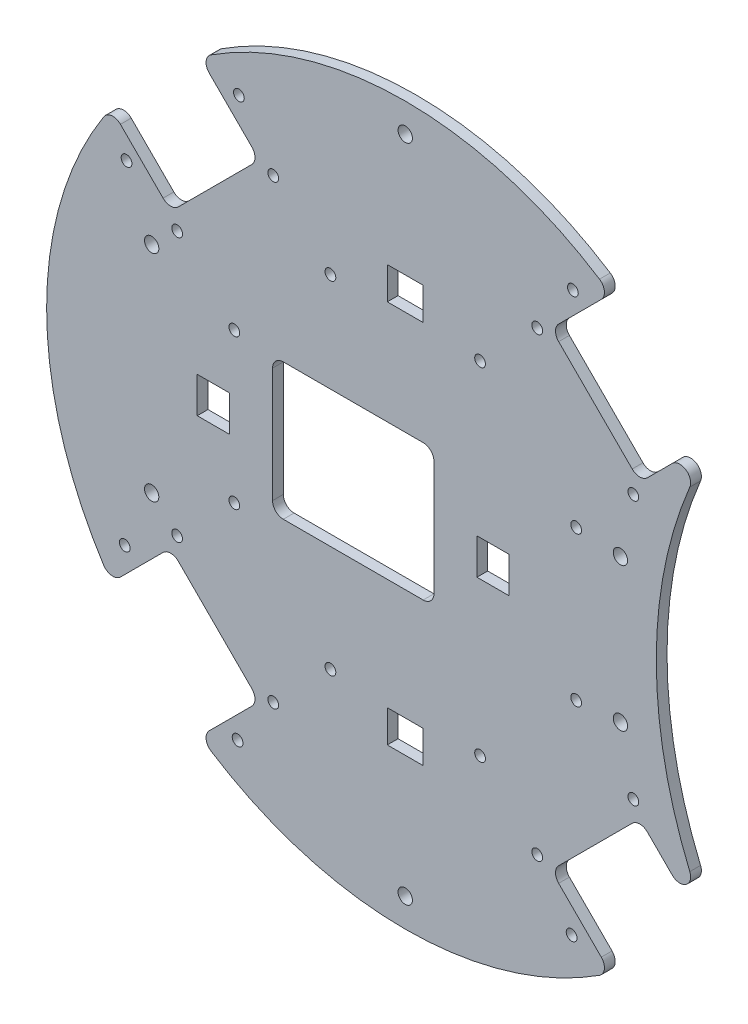
SolidWorks part; units mm, degrees
material "Caoba"
ref_plane "Alzado" through (0, 0, 0) normal (0, 0, 1) x (1, 0, 0)
ref_plane "Planta" through (0, 0, 0) normal (0, 1, 0) x (1, 0, 0)
ref_plane "Vista lateral" through (0, 0, 0) normal (1, 0, 0) x (0, 0, -1)
sketch "Croquis1" plane through (0, 0, 0) normal (0, 0, 1) x (1, 0, 0)
  circle A0 centre (0, 0) radius 100
  dimension "D1" = 200
extrude "Saliente-Extruir1" add sketch "Croquis1" along normal blind 3
sketch "Croquis3" plane through (0, 0, 3) normal (0, 0, 1) x (1, 0, 0)
  line L0 (0, 0) -> (190, 0) construction
  circle A0 centre (190, 0) radius 120
  dimension "D1" = 240
  dimension "D2" = 190
extrude "Cortar-Extruir1" cut sketch "Croquis3" against normal blind 3
sketch "Croquis5" plane through (0, 0, 3) normal (0, 0, 1) x (1, 0, 0)
  line L0 (0, -100) -> (0, 100) construction
  line L1 (-100, 0) -> (70, 0) construction
  line L2 (0, 0) -> (-70.7107, -70.7107) construction
  line L3 (-70.7107, -70.7107) -> (70.7107, 70.7107) construction
  line L4 (0, 0) -> (-70.7107, 70.7107) construction
  line L5 (-70.7107, 70.7107) -> (70.7107, -70.7107) construction
  line L6 (-70.7107, -70.7107) -> (-58.3363, -83.085) construction
  line L9 (-58.3363, -83.085) -> (-83.085, -58.3363)
  line L11 (-83.085, -58.3363) -> (-65.4074, -40.6586)
  line L12 (-65.4074, -40.6586) -> (-40.6586, -65.4074)
  line L13 (-40.6586, -65.4074) -> (-58.3363, -83.085)
  line L14 (-70.7107, 70.7107) -> (-83.085, 58.3363) construction
  line L15 (-83.085, 58.3363) -> (-100, 0) construction
  line L17 (-83.085, 58.3363) -> (-58.3363, 83.085)
  line L18 (-58.3363, 83.085) -> (-40.6586, 65.4074)
  line L19 (-40.6586, 65.4074) -> (-65.4074, 40.6586)
  line L20 (-65.4074, 40.6586) -> (-83.085, 58.3363)
  line L22 (70.7107, -70.7107) -> (58.3363, -83.085) construction
  line L23 (58.3363, -83.085) -> (0, -100) construction
  line L24 (58.3363, -83.085) -> (83.085, -58.3363)
  line L25 (83.085, -58.3363) -> (65.4074, -40.6586)
  line L26 (65.4074, -40.6586) -> (40.6586, -65.4074)
  line L27 (40.6586, -65.4074) -> (58.3363, -83.085)
  line L28 (70.7107, 70.7107) -> (58.3363, 83.085) construction
  line L29 (58.3363, 83.085) -> (0, 100) construction
  line L30 (58.3363, 83.085) -> (83.085, 58.3363)
  line L31 (83.085, 58.3363) -> (65.4074, 40.6586)
  line L32 (65.4074, 40.6586) -> (40.6586, 65.4074)
  line L33 (40.6586, 65.4074) -> (58.3363, 83.085)
  arc A0 (83.4211, 55.1446) -> (83.4211, -55.1446) centre (0, 0) ccw construction
  arc A1 (83.4211, 55.1446) -> (83.4211, -55.1446) centre (190, 0) ccw construction
  point P36 (0, 0)
  dimension "D2" = 17.5
  dimension "D3" = 25
  dimension "D4" = 35
  dimension "D5" = 25
  dimension "D6" = 35
  dimension "D8" = 25
  dimension "D9" = 17.5
  dimension "D7" = 35
  dimension "D10" = 90
  dimension "D11" = 17.5
  dimension "D12" = 17.5
  dimension "D13" = 35
  dimension "D14" = 25
  dimension "D15" = 134.3503
  dimension "D16" = 100
extrude "Cortar-Extruir6" cut sketch "Croquis5" against normal blind 10
sketch "Croquis12" plane through (0, 0, 3) normal (0, 0, 1) x (1, 0, 0)
  line L0 (-53.033, -53.033) -> (-39.9421, -50.0116) construction
  line L1 (-40.6586, -65.4074) -> (-65.4074, -40.6586) construction
  line L2 (-39.9421, -50.0116) -> (-36.8049, -63.6043) construction
  line L3 (-36.8049, -63.6043) -> (-63.6043, -36.8049) construction
  line L4 (-63.6043, -36.8049) -> (-47.6661, -20.8667) construction
  line L6 (53.033, -53.033) -> (-53.033, 53.033) construction
  line L7 (65.4074, -40.6586) -> (40.6586, -65.4074) construction
  line L8 (-65.4074, 40.6586) -> (-40.6586, 65.4074) construction
  line L9 (36.8049, 63.6043) -> (20.8667, 47.6661) construction
  line L10 (63.6043, 36.8049) -> (36.8049, 63.6043) construction
  line L11 (50.0116, 39.9421) -> (63.6043, 36.8049) construction
  line L12 (53.033, 53.033) -> (50.0116, 39.9421) construction
  line L14 (53.033, -53.033) -> (50.2046, -50.2046) construction
  line L15 (50.2046, -50.2046) -> (36.8049, -63.6043) construction
  line L16 (36.8049, -63.6043) -> (63.6043, -36.8049) construction
  line L17 (63.6043, -36.8049) -> (47.6661, -20.8667) construction
  line L19 (-53.033, -53.033) -> (53.033, 53.033) construction
  line L20 (-36.8049, 63.6043) -> (-20.8667, 47.6661) construction
  line L21 (-63.6043, 36.8049) -> (-36.8049, 63.6043) construction
  line L22 (-50.2046, 50.2046) -> (-63.6043, 36.8049) construction
  line L23 (-53.033, 53.033) -> (-50.2046, 50.2046) construction
  circle A0 centre (-63.6043, -36.8049) radius 1.5
  circle A1 centre (-36.8049, -63.6043) radius 1.5
  circle A2 centre (-47.6661, -20.8667) radius 1.5
  circle A3 centre (-20.8667, -47.6661) radius 1.5
  circle A5 centre (47.6661, 20.8667) radius 1.5
  circle A6 centre (20.8667, 47.6661) radius 1.5
  circle A7 centre (63.6043, 36.8049) radius 1.5
  circle A8 centre (36.8049, 63.6043) radius 1.5
  circle A10 centre (20.8667, -47.6661) radius 1.5
  circle A11 centre (47.6661, -20.8667) radius 1.5
  circle A12 centre (63.6043, -36.8049) radius 1.5
  circle A13 centre (36.8049, -63.6043) radius 1.5
  circle A15 centre (-63.6043, 36.8049) radius 1.5
  circle A16 centre (-36.8049, 63.6043) radius 1.5
  circle A17 centre (-20.8667, 47.6661) radius 1.5
  circle A18 centre (-47.6661, 20.8667) radius 1.5
  dimension "D2" = 3
  dimension "D3" = 3
  dimension "D4" = 4
  dimension "D5" = 4
  dimension "D6" = 3
  dimension "D7" = 3
  dimension "D8" = 37.9
  dimension "D9" = 22.54
  dimension "D10" = 22.54
  dimension "D11" = 37.9
  dimension "D12" = 18.95
  dimension "D13" = 18.95
  dimension "D14" = 3
  dimension "D15" = 3
  dimension "D16" = 3
  dimension "D17" = 3
  dimension "D18" = 37.9
  dimension "D19" = 22.54
  dimension "D20" = 22.54
  dimension "D21" = 37.9
  dimension "D22" = 4
  dimension "D1" = 13.95
extrude "Cortar-Extruir7" cut sketch "Croquis12" against normal through all
sketch "Croquis9" plane through (0, 0, 3) normal (0, 0, 1) x (1, 0, 0)
  line L0 (0, 0) -> (-100, 0) construction
  line L5 (0, 100) -> (0, -100) construction
  line L6 (20, 5) -> (29, 5)
  line L7 (20, 5) -> (20, -5)
  line L8 (20, -5) -> (29, -5)
  line L9 (29, 5) -> (29, -5)
  line L10 (-5, -49) -> (5, -49)
  line L11 (-49, 5) -> (-58, 5)
  line L12 (-49, 5) -> (-49, -5)
  line L13 (-49, -5) -> (-58, -5)
  line L14 (-58, 5) -> (-58, -5)
  line L15 (-5, 58) -> (5, 58)
  line L16 (-5, 58) -> (-5, 49)
  line L17 (-5, 49) -> (5, 49)
  line L18 (5, 58) -> (5, 49)
  line L19 (5, -58) -> (5, -49)
  line L20 (-5, -58) -> (5, -58)
  line L21 (-5, -58) -> (-5, -49)
  line L22 (0, 0) -> (70, 0) construction
  line L24 (-52.061, -4) -> (-52.0837, -4) construction
  arc A6 (-81.9939, 57.2451) -> (-81.9939, -57.2451) centre (0, 0) ccw construction
  arc A7 (83.4211, 55.1446) -> (83.4211, -55.1446) centre (190, 0) ccw construction
  dimension "D7" = 49
  dimension "D8" = 49
  dimension "D9" = 20
  dimension "D10" = 49
  dimension "D28" = 5
  dimension "D37" = 5
  dimension "D62" = 9
  dimension "D32" = 10
  dimension "D50" = 5
  dimension "D17" = 9
  dimension "D18" = 10
  dimension "D33" = 5
  dimension "D47" = 10
  dimension "D48" = 9
  dimension "D66" = 9
  dimension "D67" = 10
extrude "Cortar-Extruir5" cut sketch "Croquis9" against normal blind 10
sketch "Croquis13" plane through (0, 0, 3) normal (0, 0, 1) x (1, 0, 0)
  line L0 (0, 100) -> (0, -100) construction
  line L1 (-100, 0) -> (70, 0) construction
  line L2 (-70.7107, 70.7107) -> (70.7107, -70.7107) construction
  line L3 (-70.7093, -70.7093) -> (70.712, 70.712) construction
  line L4 (-70.7107, 70.7107) -> (-70.7093, -70.7093) construction
  line L5 (-70.7093, -70.7093) -> (70.7107, -70.7107) construction
  line L6 (70.7107, -70.7107) -> (70.712, 70.712) construction
  line L7 (70.712, 70.712) -> (-70.7107, 70.7107) construction
  line L9 (-37, 20) -> (8, 20)
  line L10 (-37, 20) -> (-37, -18)
  line L11 (-37, -18) -> (8, -18)
  line L12 (8, 20) -> (8, -18)
  arc A0 (57.2451, 81.9939) -> (-57.2451, 81.9939) centre (0, 0) ccw construction
  arc A1 (-57.2451, -81.9939) -> (57.2451, -81.9939) centre (0, 0) ccw construction
  arc A2 (-81.9939, 57.2451) -> (-81.9939, -57.2451) centre (0, 0) ccw construction
  arc A3 (83.4211, 55.1446) -> (83.4211, -55.1446) centre (190, 0) ccw construction
  circle A4 centre (-70.7103, 30) radius 2
  circle A5 centre (-70.7097, -30) radius 2
  circle A8 centre (0, -92) radius 2
  circle A9 centre (0, 92) radius 2
  circle A10 centre (60, -20) radius 2
  circle A11 centre (60, 20) radius 2
  point P37 (-15, 0)
  dimension "D9" = 4
  dimension "D10" = 4
  dimension "D11" = 30
  dimension "D12" = 30
  dimension "D13" = 4
  dimension "D14" = 4
  dimension "D15" = 60
  dimension "D16" = 60
  dimension "D17" = 4
  dimension "D18" = 92
  dimension "D19" = 92
  dimension "D20" = 4
  dimension "D25" = 20
  dimension "D26" = 20
  dimension "D1" = 45
  dimension "D2" = 200
  dimension "D3" = 0
  dimension "D4" = 200
  dimension "D5" = 45
  dimension "D6" = 0
  dimension "D7" = 141.42
  dimension "D8" = 141.42
  dimension "D21" = 45
  dimension "D22" = 38
  dimension "D23" = 18
  dimension "D24" = 37
extrude "Cortar-Extruir8" cut sketch "Croquis13" against normal through all
fillet "Redondeo2" radius 3 20 edges at (-81.9939, 57.2451, 1.5) (-65.4074, 40.6586, 1.5) (-40.6586, 65.4074, 1.5) (-57.2451, 81.9939, 1.5) (65.4074, 40.6586, 1.5) (40.6586, 65.4074, 1.5) (57.2451, 81.9939, 1.5) (81.9939, 57.2451, 1.5) (65.4074, -40.6586, 1.5) (40.6586, -65.4074, 1.5) (81.9939, -57.2451, 1.5) (57.2451, -81.9939, 1.5) (-65.4074, -40.6586, 1.5) (-81.9939, -57.2451, 1.5) (-57.2451, -81.9939, 1.5) (-40.6586, -65.4074, 1.5) (8, -18, 1.5) (8, 20, 1.5) (-37, -18, 1.5) (-37, 20, 1.5)
fillet "Redondeo3" radius 3 2 edges at (83.4211, -55.1446, 1.5) (83.4211, 55.1446, 1.5)
sketch "Croquis14" plane through (0, 0, 3) normal (0, 0, 1) x (1, 0, 0)
  line L0 (42.78, -67.5287) -> (54.6657, -79.4145) construction
  line L1 (0, 0) -> (75.1866, -75.1866) construction
  line L2 (0, 100) -> (0, -100) construction
  line L7 (-100, 0) -> (83.579, 0) construction
  line L8 (0, 0) -> (88.3883, 88.3883) construction
  line L9 (0, 0) -> (-88.3883, -88.3883) construction
  line L10 (0, 0) -> (-74.4604, 74.4604) construction
  circle A0 centre (46.3901, -78.2099) radius 1.5
  circle A2 centre (-46.7468, -77.7147) radius 1.5
  circle A3 centre (-77.7147, 46.7468) radius 1.5
  arc A12 (54.1695, 84.0575) -> (-54.1695, 84.0575) centre (0, 0) ccw construction
  arc A13 (-54.1695, -84.0575) -> (54.1695, -84.0575) centre (0, 0) ccw construction
  arc A14 (-84.0575, 54.1695) -> (-84.0575, -54.1695) centre (0, 0) ccw construction
  circle A15 centre (-78.2099, -46.3901) radius 1.5
  circle A16 centre (46.7468, 77.7147) radius 1.5
  circle A17 centre (-46.3901, 78.2099) radius 1.5
  circle A20 centre (78.2099, 46.3901) radius 1.5 [skipped]
  circle A21 centre (77.7147, -46.7468) radius 1.5 [skipped]
  point P23 (0, 0)
  dimension "D1" = 3
  dimension "D2" = 5
  dimension "D3" = 78.2099
  dimension "D4" = 3
  dimension "D5" = 77.7147
  dimension "D7" = 4
  dimension "D8" = 46.3901
  dimension "D9" = 78.2099
  dimension "D24" = 93.1369
  dimension "D6" = 125
  dimension "D19" = 125
  dimension "D20" = 45
  dimension "D21" = 45
  dimension "D22" = 45
  dimension "D23" = 45
extrude "Cortar-Extruir9" cut sketch "Croquis14" against normal through all
